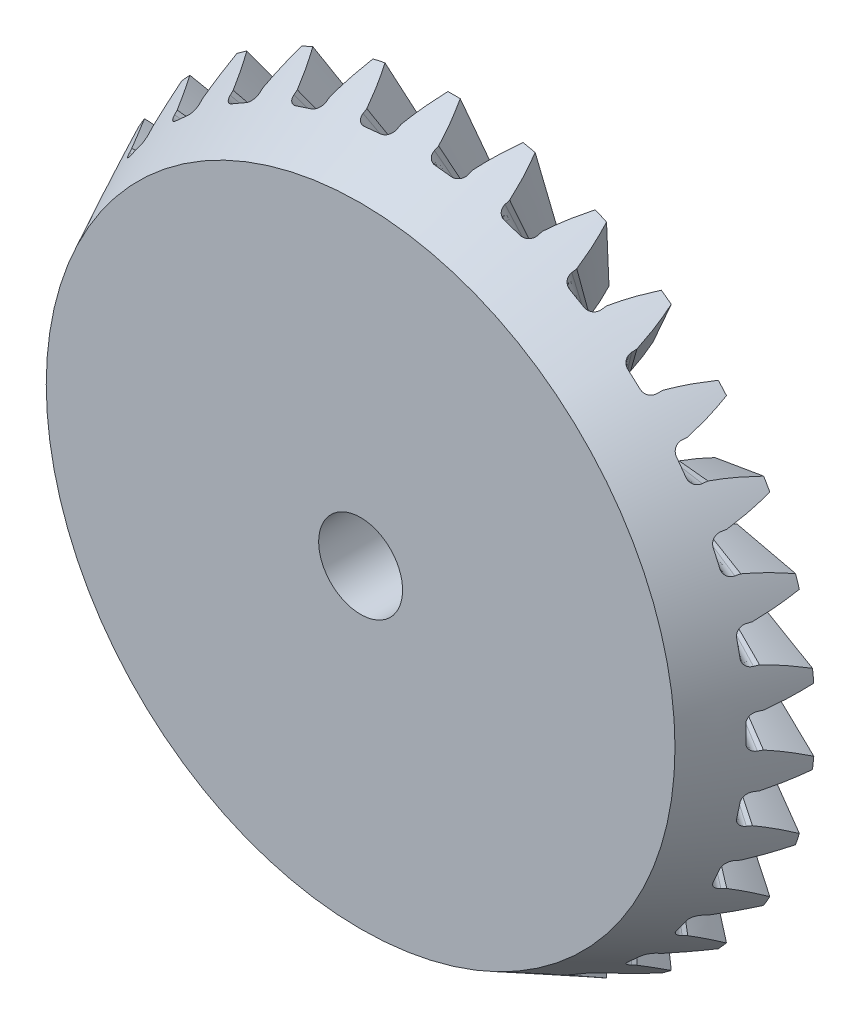
SolidWorks part; units mm, degrees
ref_plane "Front Plane" through (0, 0, 0) normal (0, 0, 1) x (1, 0, 0)
ref_plane "Top Plane" through (0, 0, 0) normal (0, 1, 0) x (1, 0, 0)
ref_plane "Right Plane" through (0, 0, 0) normal (1, 0, 0) x (0, 0, -1)
ref_axis "Gear Axis" through (0, 0, -1.8867) along (0, 0, 1)
sketch "Blank Sketch" plane through (0, 0, 0) normal (0, 1, 0) x (1, 0, 0)
  line L0 (0, 0) -> (0, -37.7336) construction
  line L1 (0, 0) -> (33.75, -16.875) construction
  line L2 (0, 0) -> (23.0169, -11.5084) construction
  line L3 (19.7149, -18.1124) -> (23.4062, -10.7298)
  line L4 (23.4062, -10.7298) -> (34.4091, -15.5568)
  line L5 (34.4091, -15.5568) -> (29.9574, -24.4601)
  line L6 (29.9574, -24.4601) -> (0, -24.4601)
  line L7 (0, -24.4601) -> (0, -18.1124)
  line L8 (0, -18.1124) -> (19.7149, -18.1124)
  line L9 (33.75, -16.875) -> (34.4091, -15.5568) construction
  line L10 (33.75, -16.875) -> (29.9574, -24.4601) construction
  line L11 (23.0169, -11.5084) -> (19.7149, -18.1124) construction
  dimension "Axis" = 37.7336
  dimension "Cone" = 63.435
  dimension "Heel" = 37.7336
  dimension "Toe Cone" = 63.435
  dimension "Toe" = 25.7336
  dimension "Heel Square" = 90
  dimension "Addendum" = 1.4737
  dimension "Root Square" = 90
  dimension "Heel Rim" = 8.4804
  dimension "Toe Square" = 90
  dimension "Toe Rim" = 7.3835
  dimension "Front Square" = 90
  dimension "Face" = 2.878
  dimension "Back" = 29.9574
  dimension "Front" = 19.7149
revolve "Blank" add sketch "Blank Sketch" angle 360 about L0
sketch "Cone Sketch" plane through (0, 0, 0) normal (0, 1, 0) x (1, 0, 0)
  line L0 (0, 0) -> (0, -37.7336) construction
  line L1 (0, 0) -> (35.7625, -17.8812)
  line L2 (0, 0) -> (21.0044, -10.5022)
  dimension "Axis" = 37.7336
  dimension "Toe Cone" = 63.435
  dimension "Heel Cone" = 63.435
  dimension "Heel" = 39.9836
  dimension "Toe" = 23.4836
ref_plane "Heel Plane" through (35.7625, 0, 17.8812) normal (0.8944, 0, 0.4472) x (0.4472, 0, -0.8944)
ref_plane "Toe Plane" through (21.0044, 0, 10.5022) normal (0.8944, 0, 0.4472) x (0.4472, 0, -0.8944)
sketch "Heel Section Sketch" plane through (35.7625, 0, 17.8812) normal (0.8944, 0, 0.4472) x (0.4472, 0, -0.8944)
  line L0 (0, 0) -> (-79.9673, 0) construction
  line L1 (-2.3155, 1.7439) -> (-2.7737, 1.7336)
  line L2 (-2.3155, -1.7439) -> (-2.7737, -1.7336)
  line L3 (3.8303, 4.4017) -> (3.8303, -4.4017)
  arc A0 (-2.7737, 1.7336) -> (-3.6593, 0.8182) centre (-2.7534, 0.8279) ccw
  arc A1 (-3.6593, -0.8182) -> (-2.7737, -1.7336) centre (-2.7534, -0.8279) ccw
  arc A2 (-3.6593, -0.8182) -> (-3.6593, 0.8182) centre (-79.9673, 0) ccw
  spline S0 degree 4 poles (-2.744, 1.6269) (-2.7139, 1.6348) (-2.656, 1.6501) (-2.5703, 1.6726) (-2.3625, 1.7303) (-2.2536, 1.7614) (-1.9817, 1.8415) (-1.815, 1.8938) (-1.5868, 1.966) (-1.3967, 2.0294) (-1.1845, 2.1011) (-0.9868, 2.1708) (-0.7813, 2.2447) (-0.5817, 2.3187) (-0.3792, 2.3956) (-0.1799, 2.4731) (0.0312, 2.5573) (0.2888, 2.6623) (0.599, 2.7931) (0.9495, 2.9454) (1.3482, 3.1267) (1.727, 3.3036) (2.1308, 3.5012) (2.4875, 3.6786) (2.9149, 3.9021) (3.2191, 4.0621) (3.6932, 4.3242) (3.8787, 4.4285) (4.163, 4.5912) (4.3066, 4.6749) (4.3738, 4.7143) (4.4114, 4.7364) knots 0 0 0 0 0 0.014246 0.028492 0.056481 0.083968 0.111456 0.138944 0.166431 0.193919 0.221407 0.248895 0.276382 0.30387 0.331358 0.358846 0.386333 0.419446 0.474422 0.529397 0.584373 0.639348 0.694324 0.749299 0.804274 0.85925 0.914226 0.957113 0.978556 1 1 1 1 1 construction
  spline S1 degree 4 poles (-2.3155, 1.7439) (-2.2712, 1.7566) (-2.1847, 1.7817) (-1.9817, 1.8415) (-1.815, 1.8938) (-1.5868, 1.966) (-1.3967, 2.0294) (-1.1845, 2.1011) (-0.9868, 2.1708) (-0.7813, 2.2447) (-0.5817, 2.3187) (-0.3792, 2.3956) (-0.1799, 2.4731) (0.0312, 2.5573) (0.2888, 2.6623) (0.599, 2.7931) (0.9495, 2.9454) (1.3482, 3.1267) (1.727, 3.3036) (2.1308, 3.5012) (2.4875, 3.6786) (2.9149, 3.9021) (3.2191, 4.0621) (3.5954, 4.2701) (3.7499, 4.3563) (3.8303, 4.4017) knots 0.056481 0.056481 0.056481 0.056481 0.056481 0.083968 0.111456 0.138944 0.166431 0.193919 0.221407 0.248895 0.276382 0.30387 0.331358 0.358846 0.386333 0.419446 0.474422 0.529397 0.584373 0.639348 0.694324 0.749299 0.804274 0.85925 0.914226 0.914226 0.914226 0.914226 0.914226
  spline S2 degree 4 poles (-2.744, -1.6269) (-2.7139, -1.6348) (-2.656, -1.6501) (-2.5703, -1.6726) (-2.3625, -1.7303) (-2.2536, -1.7614) (-1.9817, -1.8415) (-1.815, -1.8938) (-1.5868, -1.966) (-1.3967, -2.0294) (-1.1845, -2.1011) (-0.9868, -2.1708) (-0.7813, -2.2447) (-0.5817, -2.3187) (-0.3792, -2.3956) (-0.1799, -2.4731) (0.0312, -2.5573) (0.2888, -2.6623) (0.599, -2.7931) (0.9495, -2.9454) (1.3482, -3.1267) (1.727, -3.3036) (2.1308, -3.5012) (2.4875, -3.6786) (2.9149, -3.9021) (3.2191, -4.0621) (3.6932, -4.3242) (3.8787, -4.4285) (4.163, -4.5912) (4.3066, -4.6749) (4.3738, -4.7143) (4.4114, -4.7364) knots 0 0 0 0 0 0.014246 0.028492 0.056481 0.083968 0.111456 0.138944 0.166431 0.193919 0.221407 0.248895 0.276382 0.30387 0.331358 0.358846 0.386333 0.419446 0.474422 0.529397 0.584373 0.639348 0.694324 0.749299 0.804274 0.85925 0.914226 0.957113 0.978556 1 1 1 1 1 construction
  spline S3 degree 4 poles (-2.3155, -1.7439) (-2.2712, -1.7566) (-2.1847, -1.7817) (-1.9817, -1.8415) (-1.815, -1.8938) (-1.5868, -1.966) (-1.3967, -2.0294) (-1.1845, -2.1011) (-0.9868, -2.1708) (-0.7813, -2.2447) (-0.5817, -2.3187) (-0.3792, -2.3956) (-0.1799, -2.4731) (0.0312, -2.5573) (0.2888, -2.6623) (0.599, -2.7931) (0.9495, -2.9454) (1.3482, -3.1267) (1.727, -3.3036) (2.1308, -3.5012) (2.4875, -3.6786) (2.9149, -3.9021) (3.2191, -4.0621) (3.5954, -4.2701) (3.7499, -4.3563) (3.8303, -4.4017) knots 0.056481 0.056481 0.056481 0.056481 0.056481 0.083968 0.111456 0.138944 0.166431 0.193919 0.221407 0.248895 0.276382 0.30387 0.331358 0.358846 0.386333 0.419446 0.474422 0.529397 0.584373 0.639348 0.694324 0.749299 0.804274 0.85925 0.914226 0.914226 0.914226 0.914226 0.914226
  dimension "Root" = 76.3124
  dimension "Fillet" = 0.906
  dimension "Centre" = 79.9673
sketch "Toe Section Sketch" plane through (21.0044, 0, 10.5022) normal (0.8944, 0, 0.4472) x (0.4472, 0, -0.8944)
  line L0 (0, 0) -> (-46.9673, 0) construction
  line L1 (-1.36, 1.0243) -> (-1.6291, 1.0182)
  line L2 (-1.36, -1.0243) -> (-1.6291, -1.0182)
  line L3 (2.2496, 2.5852) -> (2.2496, -2.5852)
  arc A0 (-1.6291, 1.0182) -> (-2.1492, 0.4805) centre (-1.6171, 0.4862) ccw
  arc A1 (-2.1492, -0.4805) -> (-1.6291, -1.0182) centre (-1.6171, -0.4862) ccw
  arc A2 (-2.1492, -0.4805) -> (-2.1492, 0.4805) centre (-46.9673, 0) ccw
  spline S0 degree 4 poles (-1.6116, 0.9555) (-1.594, 0.9602) (-1.56, 0.9691) (-1.5096, 0.9824) (-1.3876, 1.0163) (-1.3236, 1.0345) (-1.1639, 1.0816) (-1.066, 1.1123) (-0.932, 1.1547) (-0.8203, 1.1919) (-0.6957, 1.2341) (-0.5796, 1.275) (-0.4589, 1.3184) (-0.3416, 1.3619) (-0.2227, 1.407) (-0.1057, 1.4526) (0.0183, 1.502) (0.1696, 1.5636) (0.3518, 1.6405) (0.5577, 1.7299) (0.7919, 1.8364) (1.0143, 1.9403) (1.2515, 2.0564) (1.461, 2.1605) (1.7121, 2.2918) (1.8906, 2.3858) (2.1692, 2.5398) (2.2914, 2.6085) (2.4729, 2.7126) (2.5478, 2.7565) (2.5907, 2.7817) knots 0 0 0 0 0 0.014246 0.028492 0.056481 0.083968 0.111456 0.138944 0.166431 0.193919 0.221407 0.248895 0.276382 0.30387 0.331358 0.358846 0.386333 0.419446 0.474422 0.529397 0.584373 0.639348 0.694324 0.749299 0.804274 0.85925 0.914226 0.957113 1 1 1 1 1 construction
  spline S1 degree 4 poles (-1.36, 1.0243) (-1.3339, 1.0317) (-1.2831, 1.0465) (-1.1639, 1.0816) (-1.066, 1.1123) (-0.932, 1.1547) (-0.8203, 1.1919) (-0.6957, 1.2341) (-0.5796, 1.275) (-0.4589, 1.3184) (-0.3416, 1.3619) (-0.2227, 1.407) (-0.1057, 1.4526) (0.0183, 1.502) (0.1696, 1.5636) (0.3518, 1.6405) (0.5577, 1.7299) (0.7919, 1.8364) (1.0143, 1.9403) (1.2515, 2.0564) (1.461, 2.1605) (1.7121, 2.2918) (1.8906, 2.3858) (2.1117, 2.508) (2.2025, 2.5586) (2.2496, 2.5852) knots 0.056481 0.056481 0.056481 0.056481 0.056481 0.083968 0.111456 0.138944 0.166431 0.193919 0.221407 0.248895 0.276382 0.30387 0.331358 0.358846 0.386333 0.419446 0.474422 0.529397 0.584373 0.639348 0.694324 0.749299 0.804274 0.85925 0.914226 0.914226 0.914226 0.914226 0.914226
  spline S2 degree 4 poles (-1.6116, -0.9555) (-1.594, -0.9602) (-1.56, -0.9691) (-1.5096, -0.9824) (-1.3876, -1.0163) (-1.3236, -1.0345) (-1.1639, -1.0816) (-1.066, -1.1123) (-0.932, -1.1547) (-0.8203, -1.1919) (-0.6957, -1.2341) (-0.5796, -1.275) (-0.4589, -1.3184) (-0.3416, -1.3619) (-0.2227, -1.407) (-0.1057, -1.4526) (0.0183, -1.502) (0.1696, -1.5636) (0.3518, -1.6405) (0.5577, -1.7299) (0.7919, -1.8364) (1.0143, -1.9403) (1.2515, -2.0564) (1.461, -2.1605) (1.7121, -2.2918) (1.8906, -2.3858) (2.1692, -2.5398) (2.2914, -2.6085) (2.4729, -2.7126) (2.5478, -2.7565) (2.5907, -2.7817) knots 0 0 0 0 0 0.014246 0.028492 0.056481 0.083968 0.111456 0.138944 0.166431 0.193919 0.221407 0.248895 0.276382 0.30387 0.331358 0.358846 0.386333 0.419446 0.474422 0.529397 0.584373 0.639348 0.694324 0.749299 0.804274 0.85925 0.914226 0.957113 1 1 1 1 1 construction
  spline S3 degree 4 poles (-1.36, -1.0243) (-1.3339, -1.0317) (-1.2831, -1.0465) (-1.1639, -1.0816) (-1.066, -1.1123) (-0.932, -1.1547) (-0.8203, -1.1919) (-0.6957, -1.2341) (-0.5796, -1.275) (-0.4589, -1.3184) (-0.3416, -1.3619) (-0.2227, -1.407) (-0.1057, -1.4526) (0.0183, -1.502) (0.1696, -1.5636) (0.3518, -1.6405) (0.5577, -1.7299) (0.7919, -1.8364) (1.0143, -1.9403) (1.2515, -2.0564) (1.461, -2.1605) (1.7121, -2.2918) (1.8906, -2.3858) (2.1117, -2.508) (2.2025, -2.5586) (2.2496, -2.5852) knots 0.056481 0.056481 0.056481 0.056481 0.056481 0.083968 0.111456 0.138944 0.166431 0.193919 0.221407 0.248895 0.276382 0.30387 0.331358 0.358846 0.386333 0.419446 0.474422 0.529397 0.584373 0.639348 0.694324 0.749299 0.804274 0.85925 0.914226 0.914226 0.914226 0.914226 0.914226
  dimension "Root" = 44.8206
  dimension "Fillet" = 0.5321
  dimension "Centre" = 46.9673
loft "Tooth Space" cut profiles "Heel Section Sketch", "Toe Section Sketch"
pattern_circular "Teeth" count 30 over 360 about axis through (0, 0, -1.8867) along (0, 0, 1) of "Tooth Space"
sketch "Sketch1" plane through (0, 0, 0) normal (0, 1, 0) x (1, 0, 0)
  line L0 (14.1509, 0) -> (-14.1509, 0) construction
  line L3 (0, -12.1912) -> (0, 12.1912) construction
  line L4 (0, 1.8867) -> (0, -39.6203) construction
  point P4 (0, 0)
  point P10 (0, 0)
sketch "Sketch2" plane through (0, 0, 18.1124) normal (0, 0, -1) x (-1, 0, 0)
  circle A0 centre (0, 0) radius 4
  dimension "D1" = 8
extrude "Cut-Extrude1" cut sketch "Sketch2" against normal blind 10
equation "\"No. of Teeth\"= 30"
equation "\"Module\"= 2.25"
equation "\"Bore Diameter\"= 0"
equation "\"Pressure Angle\"= 20"
equation "\"Shaft Angle\"= 90"
equation "\"Mate Teeth\"= 15"
equation "\"Pitch Cone Angle\"= IIF ( ( \"Mate Teeth\" / \"No. of Teeth\" + cos ( \"Shaft Angle\" ) ) > 0 , atn ( sin ( \"Shaft Angle\" ) / ( \"Mate Teeth\" / \"No. of Teeth\" + cos ( \"Shaft Angle\" ) ) ) , 180 + atn ( sin ( \"Shaft Angle\" ) / ( \"Mate Teeth\" / \"No. of Teeth\" + cos ( \"Shaft Angle\" ) ) ) )"
equation "\"Mate Cone Angle\"= \"Shaft Angle\" - \"Pitch Cone Angle\""
equation "\"Addendum\"= IIF ( \"No. of Teeth\" >= \"Mate Teeth\" , 0.54 * \"Module\" + 0.46 * \"Module\" / ( ( \"No. of Teeth\" * cos ( \"Mate Cone Angle\" ) ) / ( \"Mate Teeth\" * cos ( \"Pitch Cone Angle\" ) ) ) , 2 * \"Module\" - ( 0.54 * \"Module\" + 0.46 * \"Module\" / ( ( \"Mate Teeth\" * cos ( \"Pitch Cone Angle\" ) ) / ( \"No. of Teeth\" * cos ( \"Mate Cone Angle\" ) ) ) ) )"
equation "\"Outer Diameter\"= \"No. of Teeth\" * \"Module\" + 2 * \"Addendum\" * cos ( \"Pitch Cone Angle\" )"
equation "\"Pitch Diameter\"= \"No. of Teeth\" * \"Module\""
equation "\"Backlash\"= 0.3 * \"Module\""
equation "\"Arc Length\"= ( ( \"Module\" * pi ) / 2 + \"Backlash\" - 2 * ( \"Addendum\" - \"Module\" ) * tan ( \"Pressure Angle\" ) )"
equation "\"Fillet Radius\"= 0.38 * \"Module\""
equation "\"Mate Addendum\"= 2 * \"Module\" - \"Addendum\""
equation "\"Dedendum\"= 2.188 * \"Module\" - \"Addendum\""
equation "\"Tooth Depth\"= \"Addendum\" + \"Dedendum\""
equation "\"Mate Dedendum\"= 2.188 * \"Module\" - \"Mate Addendum\""
equation "\"Face Width\"= 12"
equation "\"Cone Distance\"= \"Pitch Diameter\" / ( 2 * sin ( \"Pitch Cone Angle\" ) )"
equation "\"Dedendum Angle\"= atn ( \"Dedendum\" / \"Cone Distance\" )"
equation "\"Mate Dedendum Angle\"= atn ( \"Mate Dedendum\" / \"Cone Distance\" )"
equation "\"Face Angle\"= \"Pitch Cone Angle\" + \"Mate Dedendum Angle\""
equation "\"Root Angle\"= \"Pitch Cone Angle\" - \"Dedendum Angle\""
equation "\"Overrun\"= \"Module\""
equation "\"Back Cone Pitch Diameter\"= \"Pitch Diameter\" / cos ( \"Pitch Cone Angle\" )"
equation "\"Back Cone Outer Diameter\"= \"Back Cone Pitch Diameter\" + 2 * \"Addendum\""
equation "\"Root Diameter\"= \"Back Cone Outer Diameter\" - 2 * \"Tooth Depth\""
equation "\"Base Diameter\"= \"Back Cone Pitch Diameter\" * cos ( \"Pressure Angle\" )"
equation "\"Base Radius\"= \"Base Diameter\" / 2"
equation "\"Tooth Thickness\"= \"Module\" * pi - \"Arc Length\""
equation "\"Half Space Angle\"= ( \"Arc Length\" / \"Back Cone Pitch Diameter\" ) * 180 / pi"
equation "\"Involute Fn\"= tan ( \"Pressure Angle\" ) - \"Pressure Angle\" * pi / 180"
equation "\"Flank Offset\"= \"Arc Length\" / \"Back Cone Pitch Diameter\" - \"Involute Fn\""
equation "\"Tip Cap Diameter\"= \"Back Cone Outer Diameter\" + 2 * \"Module\""
equation "\"Flank Start Diameter\"= IIF ( \"Base Diameter\" >= ( \"Root Diameter\" + 3 * \"Fillet Radius\" ) , \"Base Diameter\" , \"Root Diameter\" + 3 * \"Fillet Radius\" )"
equation "\"Involute t1\"= ( abs ( ( \"Flank Start Diameter\" / \"Base Diameter\" ) ^ 2 - 1 ) ) ^ 0.5"
equation "\"Involute t2\"= ( abs ( ( \"Tip Cap Diameter\" / \"Base Diameter\" ) ^ 2 - 1 ) ) ^ 0.5"
equation "\"Flank Arc Radius\"= ( \"Back Cone Pitch Diameter\" / 2 ) * sin ( \"Pressure Angle\" )"
equation "\"Flank Centre Angle\"= \"Half Space Angle\" + \"Pressure Angle\""
equation "\"Heel Distance\"= \"Cone Distance\" + \"Overrun\""
equation "\"Toe Distance\"= \"Cone Distance\" - \"Face Width\" - \"Overrun\""
equation "\"Heel Scale\"= \"Heel Distance\" / \"Cone Distance\""
equation "\"Toe Scale\"= \"Toe Distance\" / \"Cone Distance\""
equation "\"Heel Virtual Radius\"= \"Heel Distance\" * tan ( \"Pitch Cone Angle\" )"
equation "\"Toe Virtual Radius\"= \"Toe Distance\" * tan ( \"Pitch Cone Angle\" )"
equation "\"Axis@Blank Sketch\"= \"Cone Distance\""
equation "\"Cone@Blank Sketch\"= \"Pitch Cone Angle\""
equation "\"Heel@Blank Sketch\"= \"Cone Distance\""
equation "\"Toe Cone@Blank Sketch\"= \"Pitch Cone Angle\""
equation "\"Toe@Blank Sketch\"= \"Cone Distance\" - \"Face Width\""
equation "\"Addendum@Blank Sketch\"= \"Addendum\""
equation "\"Heel Rim@Blank Sketch\"= \"Dedendum\" + \"Module\" / cos ( \"Pitch Cone Angle\" )"
equation "\"Toe Rim@Blank Sketch\"= \"Dedendum\" - \"Face Width\" * tan ( \"Dedendum Angle\" ) + \"Module\" / cos ( \"Pitch Cone Angle\" )"
equation "\"Face@Blank Sketch\"= \"Mate Dedendum Angle\""
equation "\"Back@Blank Sketch\"= \"Cone Distance\" * sin ( \"Pitch Cone Angle\" ) - \"Dedendum\" * cos ( \"Pitch Cone Angle\" ) - \"Module\" - \"Bore Diameter\" / 2"
equation "\"Front@Blank Sketch\"= ( \"Cone Distance\" - \"Face Width\" ) * sin ( \"Pitch Cone Angle\" ) - ( \"Dedendum\" - \"Face Width\" * tan ( \"Dedendum Angle\" ) + \"Module\" / cos ( \"Pitch Cone Angle\" ) ) * cos ( \"Pitch Cone Angle\" ) - \"Bore Diameter\" / 2"
equation "\"Axis@Cone Sketch\"= \"Cone Distance\""
equation "\"Heel Cone@Cone Sketch\"= \"Pitch Cone Angle\""
equation "\"Heel@Cone Sketch\"= \"Heel Distance\""
equation "\"Toe Cone@Cone Sketch\"= \"Pitch Cone Angle\""
equation "\"Toe@Cone Sketch\"= \"Toe Distance\""
equation "\"Centre@Heel Section Sketch\"= \"Heel Virtual Radius\""
equation "\"Root@Heel Section Sketch\"= ( \"Root Diameter\" / 2 ) * \"Heel Scale\""
equation "\"Fillet@Heel Section Sketch\"= ( \"Fillet Radius\" ) * \"Heel Scale\""
equation "\"Centre@Toe Section Sketch\"= \"Toe Virtual Radius\""
equation "\"Root@Toe Section Sketch\"= ( \"Root Diameter\" / 2 ) * \"Toe Scale\""
equation "\"Fillet@Toe Section Sketch\"= ( \"Fillet Radius\" ) * \"Toe Scale\""
equation "\"Count@Teeth\"= \"No. of Teeth\""
